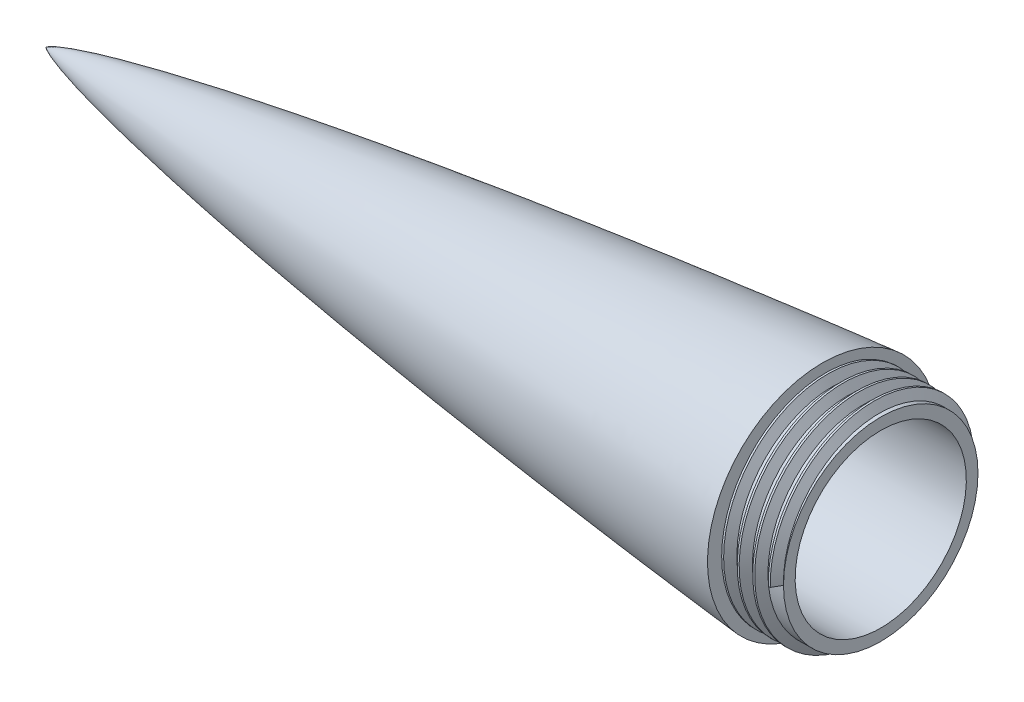
SolidWorks part; units mm, degrees
other "Markup1"
sketch "Sketch5" plane through (0, 27.3, 27.3) normal (0.8928, 0.2893, 0.3454) x (0.366, -0.0189, -0.9304)
other "Markup2"
sketch "Sketch13" plane through (0, -27.3, 27.3) normal (0.8843, -0.0281, 0.466) x (0.4595, -0.1248, -0.8794)
ref_plane "Front Plane" through (0, 0, 0) normal (0, 0, 1) x (1, 0, 0)
ref_plane "Top Plane" through (0, 0, 0) normal (0, 1, 0) x (1, 0, 0)
ref_plane "Right Plane" through (0, 0, 0) normal (1, 0, 0) x (0, 0, -1)
sketch "Sketch1" plane through (0, 0, 0) normal (0, 0, 1) x (1, 0, 0)
  line L0 (0, 33) -> (0, 38)
  line L1 (0, 38) -> (-60, 38)
  line L2 (-60, 38) -> (-60, 41.9)
  line L3 (-442.7931, 0) -> (-460, 0)
  line L4 (0, 33) -> (-153.2373, 33)
  line L7 (-153.2373, 33) -> (-153.548, 37.9903) construction
  line L8 (-442.7931, 0) -> (-443.8914, 4.8779) construction
  arc A3 (-442.7931, 0) -> (-153.2373, 33) centre (-60, -2071.9452) cw
  spline S0 degree 4 poles (-460, 0) (-459.9961, 0.0097) (-459.9858, 0.0278) (-459.957, 0.0589) (-459.9121, 0.1002) (-459.8562, 0.1434) (-459.7755, 0.2003) (-459.6835, 0.2586) (-459.5798, 0.3195) (-459.4189, 0.4076) (-459.1809, 0.5282) (-458.7776, 0.7143) (-458.0573, 1.0123) (-456.7715, 1.4835) (-454.4072, 2.2418) (-449.9638, 3.4745) (-442.1998, 5.3212) (-428.971, 8.0267) (-410.7883, 11.2204) (-388.7328, 14.6344) (-364.1908, 18.0369) (-339.6102, 21.1459) (-315.0001, 24.0108) (-290.3663, 26.6634) (-265.7124, 29.1224) (-241.0411, 31.3994) (-216.3541, 33.4998) (-191.6528, 35.424) (-170.0274, 36.9495) (-151.4833, 38.1371) (-136.0246, 39.0404) (-123.6546, 39.7078) (-111.2815, 40.3151) (-100.4523, 40.7882) (-91.1681, 41.1459) (-83.7072, 41.3976) (-78.0704, 41.5665) (-73.3455, 41.6883) (-69.5329, 41.7727) (-66.3555, 41.8304) (-63.8134, 41.8701) (-61.9067, 41.8887) (-60.6356, 41.9) (-60, 41.9) knots 0 0 0 0 0 0.000104 0.000208 0.000415 0.000609 0.000802 0.001189 0.001495 0.001802 0.002622 0.003838 0.005903 0.009538 0.016212 0.028478 0.051666 0.088742 0.150227 0.211711 0.273196 0.334681 0.396165 0.45765 0.519135 0.580619 0.642104 0.703588 0.765073 0.795815 0.826557 0.8573 0.888042 0.918784 0.934156 0.949527 0.962145 0.974763 0.981073 0.987382 0.993691 1 1 1 1 1 construction
  spline S1 degree 4 poles (-460, 0) (-459.9961, 0.0097) (-459.9858, 0.0278) (-459.957, 0.0589) (-459.9121, 0.1002) (-459.8562, 0.1434) (-459.7755, 0.2003) (-459.6835, 0.2586) (-459.5798, 0.3195) (-459.4189, 0.4076) (-459.1809, 0.5282) (-458.7776, 0.7143) (-458.0573, 1.0123) (-456.7715, 1.4835) (-454.4072, 2.2418) (-449.9638, 3.4745) (-442.1998, 5.3212) (-428.971, 8.0267) (-410.7883, 11.2204) (-388.7328, 14.6344) (-364.1908, 18.0369) (-339.6102, 21.1459) (-315.0001, 24.0108) (-290.3663, 26.6634) (-265.7124, 29.1224) (-241.0411, 31.3994) (-216.3541, 33.4998) (-191.6528, 35.424) (-170.0274, 36.9495) (-151.4833, 38.1371) (-136.0246, 39.0404) (-123.6546, 39.7078) (-111.2815, 40.3151) (-100.4523, 40.7882) (-91.1681, 41.1459) (-83.7072, 41.3976) (-78.0704, 41.5665) (-73.3455, 41.6883) (-69.5329, 41.7727) (-66.3555, 41.8304) (-63.8134, 41.8701) (-61.9067, 41.8887) (-60.6356, 41.9) (-60, 41.9) knots 0 0 0 0 0 0.000104 0.000208 0.000415 0.000609 0.000802 0.001189 0.001495 0.001802 0.002622 0.003838 0.005903 0.009538 0.016212 0.028478 0.051666 0.088742 0.150227 0.211711 0.273196 0.334681 0.396165 0.45765 0.519135 0.580619 0.642104 0.703588 0.765073 0.795815 0.826557 0.8573 0.888042 0.918784 0.934156 0.949527 0.962145 0.974763 0.981073 0.987382 0.993691 1 1 1 1 1
  dimension "D3" = 60
  dimension "D5" = 5
  dimension "D4" = 38
  dimension "D1" = 41.9
  dimension "D2" = 5
  dimension "D6" = 5
  dimension "D7" = 400
revolve "Revolve1" add sketch "Sketch1" angle 360 about L3
ref_plane "Plane1" through (-60, 0, 0) normal (1, 0, 0) x (0, 0, -1)
ref_plane "Plane2" through (-368, 0, 0) normal (1, 0, 0) x (0, 0, -1)
ref_plane "Plane3" through (-260, 0, 0) normal (1, 0, 0) x (0, 0, -1)
other "SurfaceCut1" flip cut yes
sketch "Sketch14" plane through (-260, 0, 0) normal (1, 0, 0) x (0, 0, -1)
  circle A0 centre (0, 0) radius 25.0503
  circle A1 centre (0, 0) radius 22.0503
  circle A2 centre (0, 0) radius 25.5503 construction
  dimension "D1" = 0.5
  dimension "D2" = 3
extrude "Boss-Extrude1" add sketch "Sketch14" along normal blind 15 and the other way up to surface
thread "Thread2" pitch 4 method extrude profile "Thread Profile2" start angle 0, offset 0, length 35, pitch 4, diameter 50.1007
ref_plane "Plane5" through (-245, 0, 25.0503) normal (0, -1, 0) x (0, 0, 1)
sketch "Thread Profile2" plane through (-245, 0, 25.0503) normal (0, -1, 0) x (0, 0, 1)
  line L0 (0, 0) -> (0, 4) construction
  line L1 (0, 0) -> (2.1651, 1.25)
  line L2 (2.1651, 1.25) -> (2.1651, 1.75)
  line L3 (2.1651, 1.75) -> (0, 3)
  line L4 (2.1651, 1.5) -> (0, 1.5) construction
  line L11 (0, 0) -> (0, 3)
  point P2 (0, 0)
  dimension "Pitch" = 4
  dimension "Profile_Angle" = 60
  dimension "Profile_Land" = 0.5
  dimension "Profile_Height" = 2.1651
equation "\"ConeLength\"= 400"
equation "\"D3@Sketch1\"= \"ShoulderLength\""
equation "\"ConeDiameter\"= 83.8"
equation "\"ShoulderLength\"= 60"
equation "\"ShoulderDiameter\"= 76"
equation "\"D4@Sketch1\"=\"ShoulderDiameter\"/2"
equation "\"WallThickness\"= 5"
equation "\"D5@Sketch1\"=\"WallThickness\""
equation "\"D1@Sketch1\"=\"ConeDiameter\"/2"
equation "\"ShapeParameter\"= 0"
equation "\"D2@Sketch1\"=\"WallThickness\""
equation "\"D6@Sketch1\"=\"WallThickness\""
equation "\"D7@Sketch1\"=\"ConeLength\""
